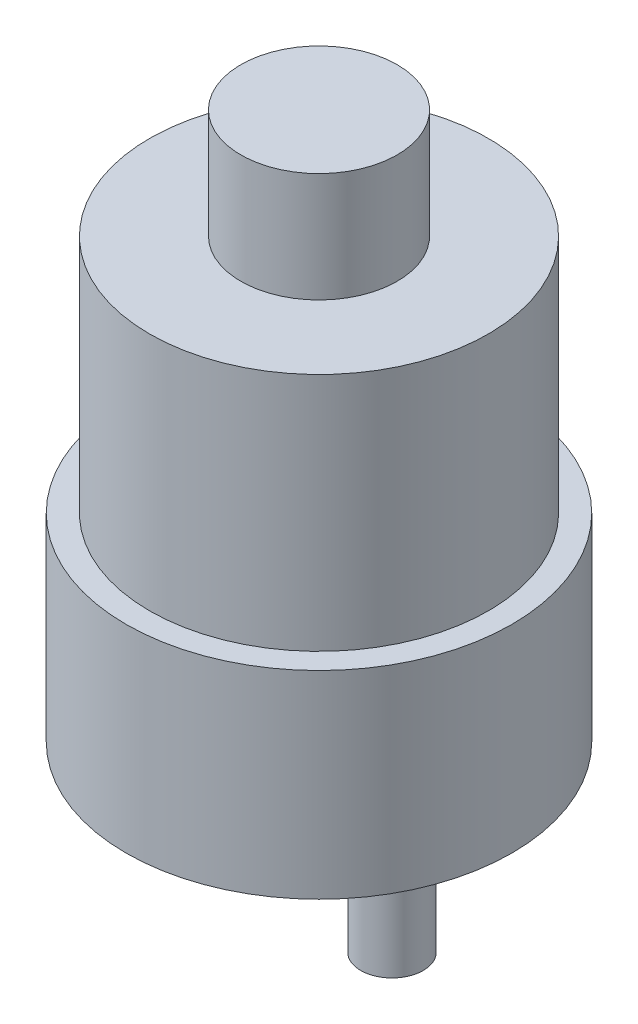
SolidWorks part; units mm, degrees
material "镀铬不锈钢"
ref_plane "前视基准面" through (0, 0, 0) normal (0, 0, 1) x (1, 0, 0)
ref_plane "上视基准面" through (0, 0, 0) normal (0, 1, 0) x (1, 0, 0)
ref_plane "右视基准面" through (0, 0, 0) normal (1, 0, 0) x (0, 0, -1)
sketch "草图1" plane through (0, 0, 0) normal (0, 1, 0) x (1, 0, 0)
  line L1 (-2.2361, 9) -> (2.2361, 9)
  circle A0 centre (0, 0) radius 18.5
  circle A2 centre (-15.5, 0) radius 1.3651
  circle A3 centre (-7.75, 13.4234) radius 1.3651
  circle A4 centre (7.75, 13.4234) radius 1.3651
  circle A5 centre (15.5, 0) radius 1.3651
  circle A6 centre (7.75, -13.4234) radius 1.3651
  circle A7 centre (-7.75, -13.4234) radius 1.3651
  circle A8 centre (0, 7) radius 6
  arc A9 (-2.2361, 9) -> (2.2361, 9) centre (0, 7) ccw
  point P18 (0, 0)
  point P24 (0, 9)
  dimension "D1" = 6
  dimension "D2" = 7
  dimension "D3" = 37
extrude "凸台-拉伸4" add sketch "草图1" along normal blind 19 contours A0 A8 A7 A6 A5 A4 A3 A2 | A8 A9 L1 | L1 A9 | A6 | A7 | A2 | A3 | A4 | A5 region at (0, 0, -6.704) region at (0, 0, 0.854) region at (-15.5, 0, 0) region at (-7.75, 0, -13.4234) region at (7.75, 0, -13.4234) region at (15.5, 0, 0) region at (7.75, 0, 13.4234) region at (-7.75, 0, 13.4234) region at (-5.8303, 0, -7)
extrude "凸台-拉伸5" add sketch "草图1<4>" against normal blind 6 contours A8 A9 L1 | L1 A9 region at (0, 0, -6.704) region at (-5.8303, 0, -7)
sketch "草图1<4>" plane through (0, 0, 0) normal (0, 1, 0) x (1, 0, 0) same geometry as "草图1"
extrude "凸台-拉伸6" add sketch "草图1<5>" against normal blind 21 contours A9 L1
sketch "草图1<5>" plane through (0, 0, 0) normal (0, 1, 0) x (1, 0, 0) same geometry as "草图1"
extrude "切除-拉伸2" cut sketch "草图1<6>" along normal blind 6 contours A5 | A6 | A7 | A2 | A3 | A4
sketch "草图1<6>" plane through (0, 0, 0) normal (0, 1, 0) x (1, 0, 0) same geometry as "草图1"
ref_plane "基准面5" through (0, 19, 0) normal (0, 1, 0) x (1, 0, 0)
sketch "草图5" plane through (0, 19, 0) normal (0, 1, 0) x (1, 0, 0)
  circle A0 centre (0, 0) radius 16.25
extrude "凸台-拉伸8" add sketch "草图5" along normal blind 23
ref_plane "基准面6" through (0, 42, 0) normal (0, 1, 0) x (1, 0, 0)
sketch "草图6" plane through (0, 42, 0) normal (0, 1, 0) x (1, 0, 0)
  circle A0 centre (0, 0) radius 7.5
extrude "凸台-拉伸10" add sketch "草图6" along normal blind 10.5
